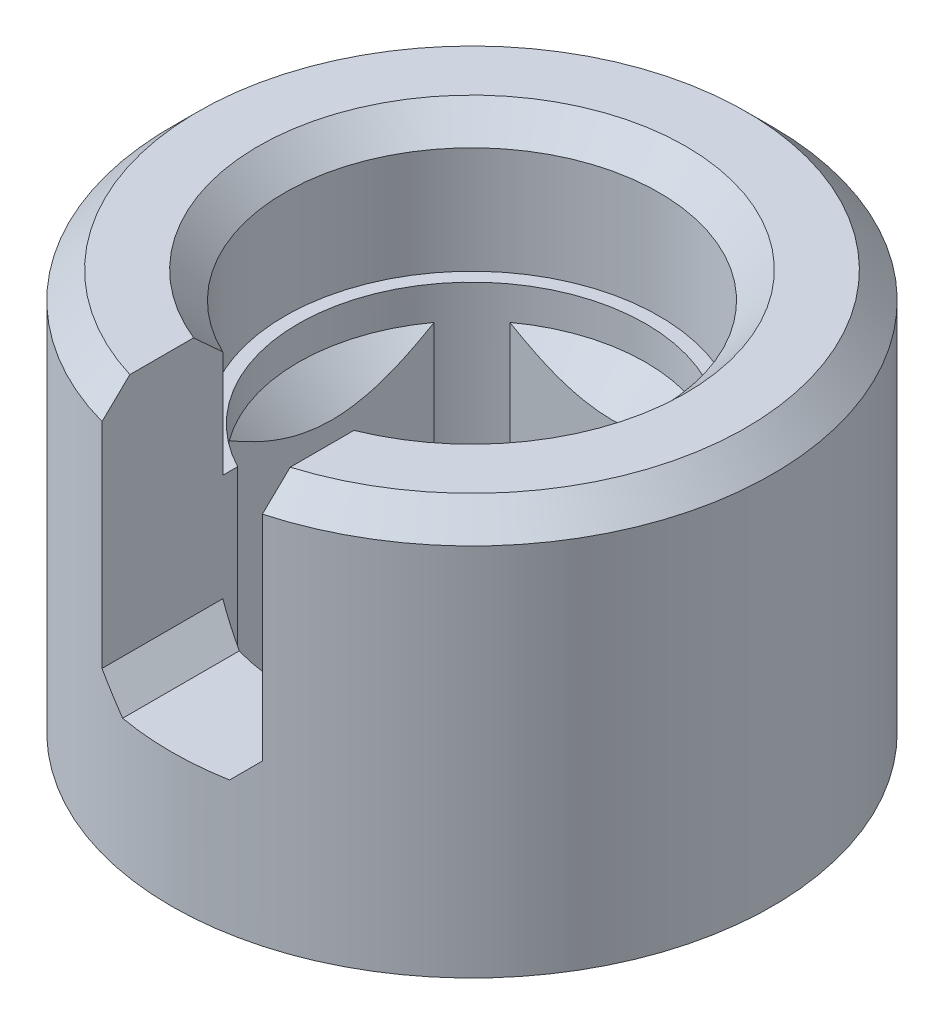
SolidWorks part; units mm, degrees
ref_plane "Front Plane" through (0, 0, 0) normal (0, 0, 1) x (1, 0, 0)
ref_plane "Top Plane" through (0, 0, 0) normal (0, 1, 0) x (1, 0, 0)
ref_plane "Right Plane" through (0, 0, 0) normal (1, 0, 0) x (0, 0, -1)
sketch "Sketch1" plane through (0, 0, 0) normal (0, 1, 0) x (1, 0, 0)
  line L0 (-6, -11.5326) -> (-6, -12.6491)
  line L1 (6, -11.5326) -> (6, -12.6491)
  line L2 (0, 0) -> (0, -13) construction
  arc A0 (6, -12.6491) -> (-6, -12.6491) centre (0, 0) ccw
  arc A1 (6, -11.5326) -> (-6, -11.5326) centre (0, 0) ccw
  point P8 (0, 0)
  dimension "D1" = 28
  dimension "D2" = 1
  dimension "D3" = 12
extrude "Boss-Extrude1" add sketch "Sketch1" along normal blind 20
sketch "Sketch2" plane through (0, 0, 0) normal (0, 1, 0) x (1, 0, 0)
  line L0 (10.5, -7.6649) -> (10.5, 7.6649)
  line L1 (-7.6649, 10.5) -> (7.6649, 10.5)
  line L2 (-10.5, 7.6649) -> (-10.5, -7.6649)
  arc A0 (6, -11.5326) -> (-6, -11.5326) centre (0, 0) ccw construction
  arc A1 (10.5, -7.6649) -> (10.5, 7.6649) centre (0, 0) ccw
  arc A2 (7.6649, 10.5) -> (-7.6649, 10.5) centre (0, 0) ccw
  arc A3 (-10.5, 7.6649) -> (-10.5, -7.6649) centre (0, 0) ccw
  dimension "D1" = 21
extrude "Boss-Extrude2" add sketch "Sketch2" along normal blind 15
chamfer "Chamfer1" distance 2.5 angle 45 3 edges at (13, 15, 0) (0, 15, -13) (-13, 15, 0)
sketch "Sketch3" plane through (0, 0, 0) normal (0, 1, 0) x (1, 0, 0)
  circle A0 centre (0, 0) radius 22.5
  circle A1 centre (0, 0) radius 14
  dimension "D1" = 45
extrude "Boss-Extrude3" add sketch "Sketch3" along normal blind 30
sketch "Sketch4" plane through (0, 20, 0) normal (0, 1, 0) x (1, 0, 0)
  line L1 (-6, -12.6491) -> (6, -12.6491)
  line L2 (-6, -12.6491) -> (-6, -25.0137)
  line L3 (-6, -25.0137) -> (6, -25.0137)
  line L4 (6, -12.6491) -> (6, -25.0137)
  circle A0 centre (0, 0) radius 14 construction
  point P5 (5.5607, -12.8483)
extrude "Cut-Extrude1" cut sketch "Sketch4" against normal blind 10 and the other way through all
chamfer "Chamfer2" distance 2 angle 45 4 edges at (0, 30, -14) (0, 30, -22.5) (6, 10, 17.1672) (-6, 10, 17.1672)
